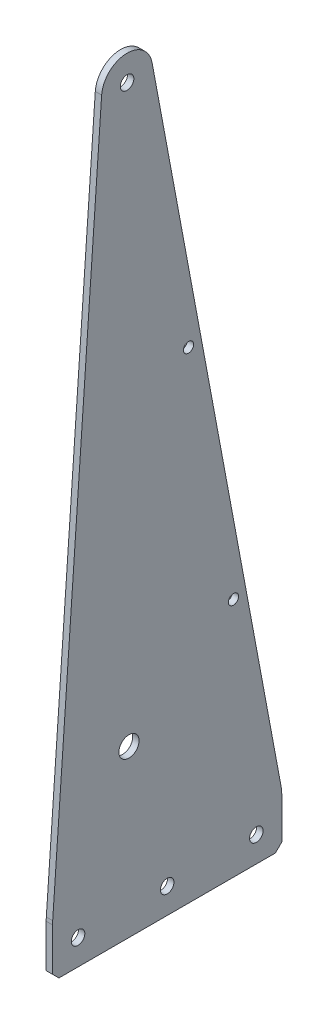
SolidWorks part; units mm, degrees
material "6061-T6 (SS)"
ref_plane "Front" through (0, 0, 0) normal (0, 0, 1) x (1, 0, 0)
ref_plane "Top" through (0, 0, 0) normal (0, 1, 0) x (1, 0, 0)
ref_plane "Right" through (0, 0, 0) normal (1, 0, 0) x (0, 0, -1)
sketch "Sketch1" plane through (0, 0, 0) normal (1, 0, 0) x (0, 0, -1)
  line L5 (63.5, 82.55) -> (-348.9452, 11.9126) construction
  line L6 (63.5, 82.55) -> (-7.1374, 494.9952) construction
  line L7 (62.5404, 369.6534) -> (22.2931, 141.3996) construction
  line L8 (22.2931, 141.3996) -> (4.6504, 41.3431) construction
  line L9 (63.5, 82.55) -> (4.6504, 41.3431) construction
  line L10 (4.6504, 41.3431) -> (-0.5288, 71.5841) construction
  line L11 (63.5, 82.55) -> (22.2931, 141.3996) construction
  line L12 (22.2931, 141.3996) -> (52.5341, 146.5788) construction
  circle A0 centre (63.5, 82.55) radius 5.0419
  dimension "D1" = 10.0838
  dimension "D3" = 63.5
  dimension "D2" = 82.55
  dimension "D4" = 80
  dimension "D7" = 70.6374
  dimension "D8" = 412.4452
  dimension "D9" = 90
  dimension "D10" = 101.6
  dimension "D11" = 231.775
sketch "Sketch2" plane through (0, 0, 0) normal (1, 0, 0) x (0, 0, -1)
  line L0 (25.4, 0) -> (25.4, 25.4)
  line L2 (25.4, 0) -> (139.7, 0)
  line L3 (139.7, 0) -> (139.7, 25.4)
  line L4 (139.7, 25.4) -> (75.0249, 371.9831)
  line L6 (25.4, 25.4) -> (49.8722, 370.5516)
  arc A0 (75.0249, 371.9831) -> (49.8722, 370.5516) centre (62.5404, 369.6534) ccw
  circle A2 centre (63.5, 82.55) radius 5.0419 construction
  circle A3 centre (63.5, 82.55) radius 5.0419
  circle A4 centre (62.5404, 369.6534) radius 3.3782
  dimension "D3" = 12.7
  dimension "D4" = 6.7564
  dimension "D5" = 25.4
  dimension "D1" = 25.4
  dimension "D2" = 139.7
extrude "Boss-Extrude2" add sketch "Sketch2" along normal blind 3.175
sketch "Sketch3" plane through (3.175, 0, 0) normal (1, 0, 0) x (0, 0, -1)
  line L0 (25.4, 0) -> (139.7, 0) construction
  line L1 (25.4, 25.4) -> (25.4, 0) construction
  line L2 (139.7, 0) -> (139.7, 25.4) construction
  line L3 (38.1, 12.7) -> (127, 12.7) construction
  line L4 (139.7, 25.4) -> (75.0249, 371.9831) construction
  line L5 (115.5869, 120.0021) -> (93.1936, 240.0042) construction
  line L6 (93.1936, 240.0042) -> (70.8002, 360.0063) construction
  line L7 (115.5869, 120.0021) -> (137.9802, 0) construction
  circle A0 centre (38.1, 12.7) radius 3.3782
  circle A1 centre (82.55, 12.7) radius 3.3782
  circle A2 centre (127, 12.7) radius 3.3782
  circle A3 centre (93.1936, 240.0042) radius 2.54
  circle A4 centre (115.5869, 120.0021) radius 2.54
  arc A5 (75.0249, 371.9831) -> (49.8722, 370.5516) centre (62.5404, 369.6534) ccw construction
  dimension "D1" = 12.7
  dimension "D2" = 12.7
  dimension "D3" = 12.7
  dimension "D4" = 6.7564
  dimension "D5" = 6.35
  dimension "D6" = 6.35
  dimension "D7" = 5.08
extrude "Cut-Extrude1" cut sketch "Sketch3" against normal through all
chamfer "Chamfer1" distance 3.175 angle 45 2 edges at (1.5875, 0, -25.4) (1.5875, 0, -139.7)
fillet "Fillet1" radius 25.4 2 edges at (1.5875, 25.4, -139.7) (1.5875, 25.4, -25.4)
